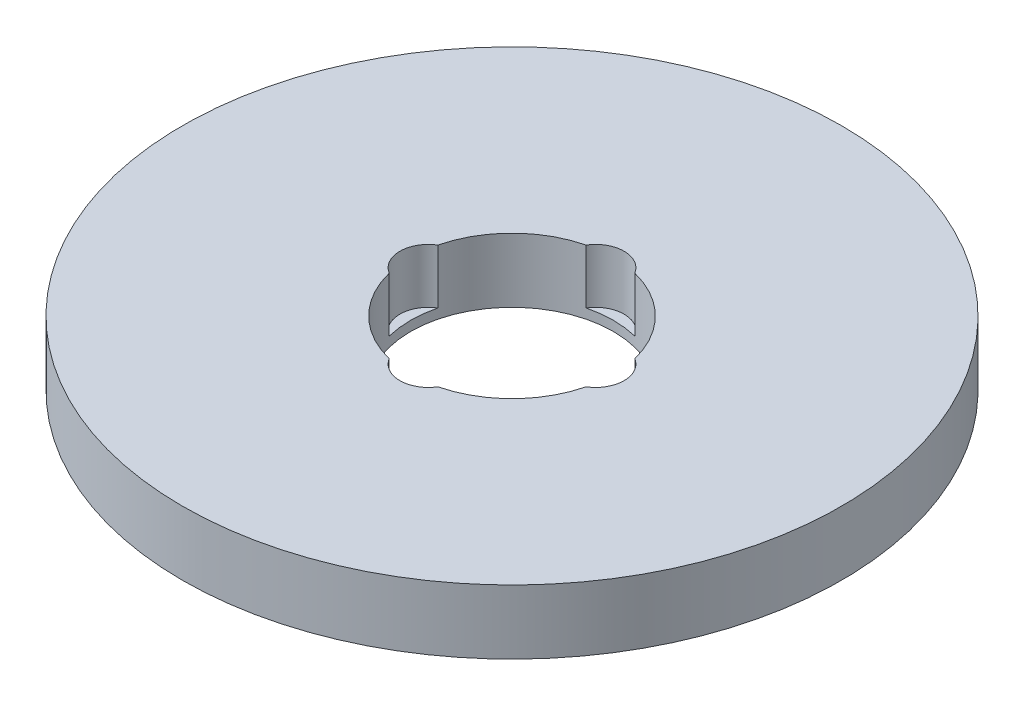
SolidWorks part; units mm, degrees
ref_plane "Front Plane" through (0, 0, 0) normal (0, 0, 1) x (1, 0, 0)
ref_plane "Top Plane" through (0, 0, 0) normal (0, 1, 0) x (1, 0, 0)
ref_plane "Right Plane" through (0, 0, 0) normal (1, 0, 0) x (0, 0, -1)
sketch "Sketch1" plane through (0, 0, 0) normal (0, 1, 0) x (1, 0, 0)
  circle A0 centre (0, 0) radius 97.5
  dimension "FLANGE_OD" = 195
extrude "Boss-Extrude1" add sketch "Sketch1" along normal blind 19
sketch "Sketch2" plane through (0, 0, 0) normal (0, 1, 0) x (1, 0, 0)
  circle A0 centre (0, 0) radius 30
  dimension "BORE_D" = 60
extrude "Cut-Extrude1" cut sketch "Sketch2" along normal through all
sketch "Sketch3" plane through (0, 19, 0) normal (0, 1, 0) x (1, 0, 0)
  circle A0 centre (0, 0) radius 24.7238 construction
  circle A1 centre (-24.7238, 0) radius 8.441
  dimension "BOLT_D" = 16.8821
  dimension "BOLT_PCD" = 49.4477
extrude "Cut-Extrude2" cut sketch "Sketch3" against normal blind 16.1271
pattern_circular "CirPattern1" count 4 over 360 about axis through (0, 0, 0) along (0, 1, 0) of "Cut-Extrude2"
